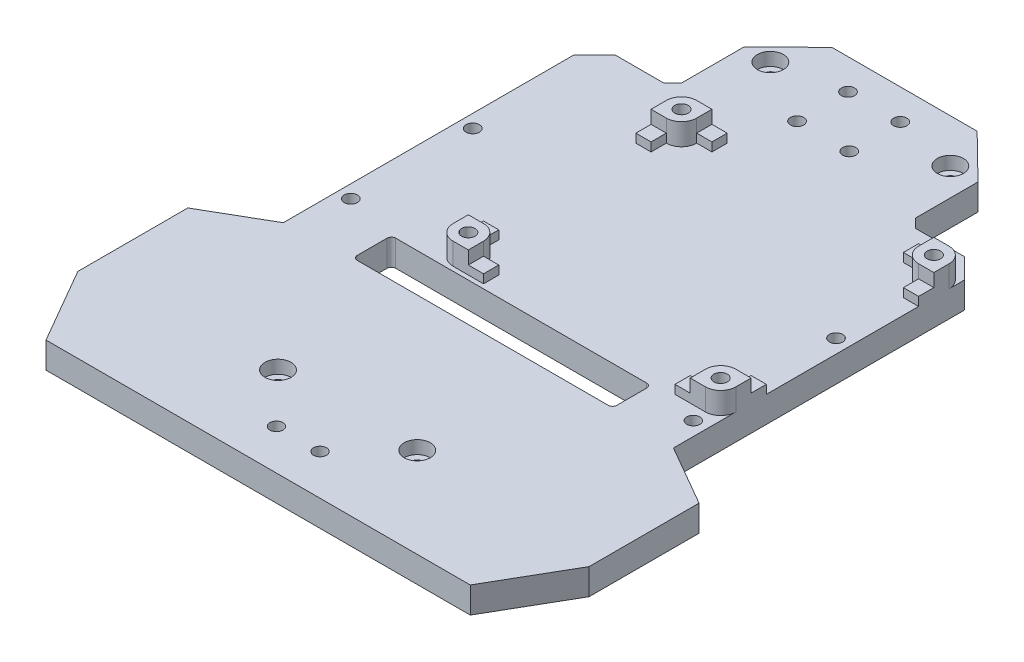
SolidWorks part; units mm, degrees
ref_plane "Front Plane" through (0, 0, 0) normal (0, 0, 1) x (1, 0, 0)
ref_plane "Top Plane" through (0, 0, 0) normal (0, 1, 0) x (1, 0, 0)
ref_plane "Right Plane" through (0, 0, 0) normal (1, 0, 0) x (0, 0, -1)
sketch "Sketch1" plane through (0, 0, 0) normal (0, 1, 0) x (1, 0, 0)
  line L0 (-16.6006, 74.2677) -> (-26.8006, 64.2675)
  line L1 (-26.8006, 64.2675) -> (-26.8006, 54.2675)
  line L2 (-26.8006, 54.2675) -> (-26.8006, 49.871)
  line L6 (-44.7582, 18.0684) -> (-44.7582, -12.842)
  line L8 (-40.1172, -36.8925) -> (-40.1172, -74.3125)
  line L9 (-40.1172, -74.3125) -> (0.0828, -74.3125)
  line L10 (0.0828, -74.3125) -> (0.0828, 74.2677) construction
  line L11 (-16.6006, 74.2677) -> (0.0828, 74.2677)
  line L12 (16.7662, 74.2677) -> (0.0828, 74.2677)
  line L13 (40.2828, -74.3125) -> (0.0828, -74.3125)
  line L14 (40.2828, -36.8925) -> (40.2828, -74.3125)
  line L16 (44.9239, 18.0684) -> (44.9239, -12.842)
  line L20 (26.9662, 54.2675) -> (26.9662, 49.871)
  line L21 (26.9662, 64.2675) -> (26.9662, 54.2675)
  line L22 (16.7662, 74.2677) -> (26.9662, 64.2675)
  line L35 (-12.597, 23.398) -> (13.1864, 23.398)
  line L36 (13.1864, 23.398) -> (13.1864, -18.272)
  line L37 (-12.597, -18.272) -> (13.1864, -18.272)
  line L38 (-12.597, 23.398) -> (-12.597, -18.272)
  line L39 (24.4264, 23.398) -> (28.1864, 23.398)
  line L40 (28.1864, 23.398) -> (28.1864, -18.272)
  line L41 (24.4264, -18.272) -> (28.1864, -18.272)
  line L42 (24.4264, 23.398) -> (24.4264, -18.272)
  line L43 (-23.837, 23.398) -> (-27.597, 23.398)
  line L44 (-27.597, 23.398) -> (-27.597, -18.272)
  line L45 (-23.837, -18.272) -> (-27.597, -18.272)
  line L46 (-23.837, 23.398) -> (-23.837, -18.272)
  line L47 (-44.7582, 18.0684) -> (-44.7582, 43.158)
  line L48 (-44.7582, 43.158) -> (-40.0718, 47.8443)
  line L49 (-40.0718, 47.8443) -> (-28.8272, 47.8443)
  line L50 (-28.8272, 47.8443) -> (-26.8006, 49.871)
  line L51 (44.9239, 18.0684) -> (44.9239, 43.158)
  line L52 (44.9239, 43.158) -> (40.2375, 47.8443)
  line L53 (40.2375, 47.8443) -> (28.9928, 47.8443)
  line L54 (28.9928, 47.8443) -> (26.9662, 49.871)
  line L55 (-40.1172, -36.8925) -> (-44.7582, -32.2514)
  line L56 (-44.7582, -32.2514) -> (-44.7582, -12.842)
  line L57 (40.2828, -36.8925) -> (44.9239, -32.2514)
  line L58 (44.9239, -32.2514) -> (44.9239, -12.842)
  dimension "D1" = 135
  dimension "D2" = 56
  dimension "D3" = 45
extrude "Boss-Extrude1" add sketch "Sketch1" along normal blind 6 contours L0 L1 L2 L50 L49 L48 L47 L6 L56 L55 L8 L9 L13 L14 L57 L58 L16 L51 L52 L53 L54 L20 L21 L22 L12 L11
sketch "Sketch2" plane through (0, 6, 0) normal (0, 1, 0) x (1, 0, 0)
  circle A0 centre (-20.7606, 64.2675) radius 1.525
  circle A1 centre (20.6062, 64.2675) radius 1.525
  circle A2 centre (-16.0772, -53.5825) radius 1.525
  circle A3 centre (15.9228, -53.5825) radius 1.525
  point P9 (-20.7606, 64.2675)
  dimension "D1" = 3.05
  dimension "D2" = 6.04
extrude "Cut-Extrude1" cut sketch "Sketch2" against normal blind 7
sketch "Sketch3" plane through (0, 6, 0) normal (0, 1, 0) x (1, 0, 0)
  circle A0 centre (-20.7606, 64.2675) radius 3
  circle A1 centre (20.6062, 64.2675) radius 3
  circle A2 centre (-16.0772, -53.5825) radius 3
  circle A3 centre (15.9228, -53.5825) radius 3
  dimension "D1" = 6
  dimension "D2" = 6
  dimension "D3" = 6
  dimension "D4" = 6
extrude "Cut-Extrude2" cut sketch "Sketch3" against normal blind 3
sketch "Sketch4" plane through (0, 6, 0) normal (0, 1, 0) x (1, 0, 0)
  line L0 (41.4239, 36.158) -> (41.4239, -5.842)
  line L1 (-13.0761, 39.658) -> (37.9239, 39.658)
  line L2 (-20.0761, 43.158) -> (44.9239, 43.158)
  line L3 (-20.0761, 43.158) -> (-20.0761, -12.842)
  line L4 (-20.0761, -12.842) -> (44.9239, -12.842)
  line L5 (44.9239, 43.158) -> (44.9239, -12.842)
  line L6 (-16.5761, 36.158) -> (-16.5761, -5.842)
  line L7 (-13.0761, -9.342) -> (37.9239, -9.342)
  circle A0 centre (-16.5761, 39.658) radius 1.55
  circle A1 centre (41.4239, 39.658) radius 1.55
  circle A2 centre (41.4239, -9.342) radius 1.55
  circle A3 centre (-16.5761, -9.342) radius 1.55
  arc A4 (37.9239, 39.658) -> (41.4239, 36.158) centre (41.4239, 39.658) ccw
  arc A5 (41.4239, -5.842) -> (37.9239, -9.342) centre (41.4239, -9.342) ccw
  arc A6 (-13.0761, -9.342) -> (-16.5761, -5.842) centre (-16.5761, -9.342) ccw
  arc A7 (-16.5761, 36.158) -> (-13.0761, 39.658) centre (-16.5761, 39.658) ccw
  dimension "D1" = 3.1
  dimension "D10" = 3.5
  dimension "D11" = 3.5
  dimension "D12" = 3.5
  dimension "D13" = 3.5
  dimension "D2" = 3.5
  dimension "D3" = 3.5
  dimension "D4" = 3.5
  dimension "D5" = 3.5
  dimension "D6" = 3.5
  dimension "D7" = 3.5
  dimension "D8" = 3.5
  dimension "D9" = 3.5
  dimension "D14" = 42
  dimension "D15" = 51
  dimension "D16" = 3.5
extrude "Boss-Extrude3" add sketch "Sketch4" along normal blind 2
fillet "Fillet1" radius 3.5 4 edges at (-20.0761, 7, -43.158) (44.9239, 7, -43.158) (-20.0761, 7, 12.842) (44.9239, 7, 12.842) tangent propagation no
sketch "Sketch5" plane through (-20.0761, 0, 0) normal (-1, 0, 0) x (0, 0, 1)
  line L0 (-39.658, 8) -> (9.342, 8) construction
  line L1 (-32.658, 8) -> (2.342, 8)
  line L2 (-32.658, 8) -> (-32.658, 6)
  line L3 (-32.658, 6) -> (2.342, 6)
  line L4 (2.342, 8) -> (2.342, 6)
  line L5 (-39.658, 6) -> (9.342, 6) construction
  point P8 (-15.158, 8)
  dimension "D1" = 35
extrude "Cut-Extrude3" cut sketch "Sketch5" against normal through all both and the other way through all
extrude "Cut-Extrude4" cut sketch "Sketch4<2>" against normal through all both and the other way through all contours A0 | A1 | A2 | A3
sketch "Sketch4<2>" plane through (0, 6, 0) normal (0, 1, 0) x (1, 0, 0) same geometry as "Sketch4"
sketch "Sketch6" plane through (0, 0, 12.842) normal (0, 0, 1) x (1, 0, 0)
  line L0 (-16.5761, 8) -> (41.4239, 8) construction
  line L1 (-9.5761, 8) -> (34.4239, 8)
  line L2 (-9.5761, 8) -> (-9.5761, 6)
  line L3 (-9.5761, 6) -> (34.4239, 6)
  line L4 (34.4239, 8) -> (34.4239, 6)
  line L5 (-16.5761, 6) -> (41.4239, 6) construction
  dimension "D1" = 3.5
  dimension "D2" = 3.5
extrude "Cut-Extrude5" cut sketch "Sketch6" against normal through all both and the other way through all
sketch "Sketch8" plane through (0, 8, 0) normal (0, 1, 0) x (1, 0, 0)
  line L0 (-13.0761, -9.342) -> (-13.0761, -12.842)
  line L1 (-16.5761, -5.842) -> (-20.0761, -5.842)
  line L2 (12.4239, -12.842) -> (12.4239, 51.535) construction
  line L3 (-9.5761, -9.342) -> (-9.5761, -12.842) construction
  line L5 (-20.0761, 15.158) -> (43.7995, 15.158) construction
  line L6 (-9.5761, -12.842) -> (-9.5761, -9.342)
  line L7 (-9.5761, -9.342) -> (-13.0761, -9.342)
  line L8 (-16.5761, -5.842) -> (-16.5761, -2.342)
  line L9 (-16.5761, -2.342) -> (-20.0761, -2.342)
  line L10 (-20.0761, -2.342) -> (-20.0761, -9.342)
  line L11 (-16.5761, -12.842) -> (-9.5761, -12.842)
  line L16 (-20.0761, -5.842) -> (-20.0761, -9.342)
  line L17 (-16.5761, -12.842) -> (-13.0761, -12.842)
  line L18 (44.9239, -2.342) -> (41.4239, -2.342) construction
  line L20 (41.4239, -12.842) -> (37.9239, -12.842)
  line L21 (44.9239, -5.842) -> (44.9239, -9.342)
  line L22 (41.4239, -5.842) -> (44.9239, -5.842)
  line L23 (37.9239, -9.342) -> (37.9239, -12.842)
  line L24 (-16.5761, 43.158) -> (-13.0761, 43.158)
  line L25 (-20.0761, 36.158) -> (-20.0761, 39.658)
  line L26 (-16.5761, 36.158) -> (-20.0761, 36.158)
  line L27 (-13.0761, 39.658) -> (-13.0761, 43.158)
  line L28 (37.9239, 39.658) -> (37.9239, 43.158)
  line L29 (41.4239, 36.158) -> (44.9239, 36.158)
  line L30 (44.9239, 36.158) -> (44.9239, 39.658)
  line L31 (41.4239, 43.158) -> (37.9239, 43.158)
  arc A0 (44.9239, -9.342) -> (41.4239, -12.842) centre (41.4239, -9.342) cw
  arc A1 (37.9239, -9.342) -> (41.4239, -5.842) centre (41.4239, -9.342) cw
  arc A2 (-13.0761, -9.342) -> (-16.5761, -5.842) centre (-16.5761, -9.342) ccw
  arc A3 (-20.0761, -9.342) -> (-16.5761, -12.842) centre (-16.5761, -9.342) ccw
  arc A4 (-13.0761, -9.342) -> (-16.5761, -5.842) centre (-16.5761, -9.342) ccw
  arc A5 (-20.0761, -9.342) -> (-16.5761, -12.842) centre (-16.5761, -9.342) ccw
  arc A6 (-20.0761, 39.658) -> (-16.5761, 43.158) centre (-16.5761, 39.658) cw
  arc A7 (-13.0761, 39.658) -> (-16.5761, 36.158) centre (-16.5761, 39.658) cw
  arc A8 (37.9239, 39.658) -> (41.4239, 36.158) centre (41.4239, 39.658) ccw
  arc A9 (44.9239, 39.658) -> (41.4239, 43.158) centre (41.4239, 39.658) ccw
  circle A10 centre (-16.5761, -9.342) radius 1.55
  circle A11 centre (41.4239, -9.342) radius 1.55
  circle A12 centre (-16.5761, 39.658) radius 1.55
  circle A13 centre (41.4239, 39.658) radius 1.55
  dimension "D2" = 22
  dimension "D3" = 17.5
  dimension "D1" = 0
extrude "Boss-Extrude4" add sketch "Sketch8" along normal blind 3
sketch "Sketch9" plane through (0, 6, 0) normal (0, 1, 0) x (1, 0, 0)
  circle A0 centre (-5.9172, 67.2677) radius 1.525
  circle A1 centre (6.0828, 67.2677) radius 1.525
  circle A2 centre (-5.9172, 55.5577) radius 1.525
  circle A3 centre (6.0828, 55.5577) radius 1.525
  dimension "D1" = 2
extrude "Cut-Extrude6" cut sketch "Sketch9" against normal blind 10
sketch "Sketch10" plane through (0, 6, 0) normal (0, 1, 0) x (1, 0, 0)
  line L0 (-44.7582, -32.2514) -> (-44.7582, 43.158) construction
  circle A0 centre (-41.7582, -11.1575) radius 1.525
  circle A1 centre (-41.7582, 16.8425) radius 1.525
  circle A2 centre (-41.7582, -11.1575) radius 1.525
  circle A3 centre (-41.7582, 16.8425) radius 1.525
  circle A4 centre (41.7582, 16.8425) radius 1.525
  circle A6 centre (-16.0772, -53.5825) radius 1.525 construction
  circle A7 centre (41.7582, -15.9575) radius 1.5
  point P10 (-41.7582, 2.8425)
  dimension "D1" = 3.05
  dimension "D7" = 3
  dimension "D2" = 3
  dimension "D3" = 56.425
  dimension "D4" = 14
  dimension "D5" = 28
  dimension "D6" = 32.8
extrude "Cut-Extrude7" cut sketch "Sketch10" against normal through all contours A0 | A1 | A4 | A7
sketch "Sketch11" plane through (0, 6, 0) normal (0, 1, 0) x (1, 0, 0)
  line L0 (40.2828, -74.3125) -> (-40.1172, -74.3125) construction
  line L1 (0, -6.05) -> (0, 6.05) construction
  circle A0 centre (-5, -65.0125) radius 1.5
  circle A1 centre (5, -65.0125) radius 1.5
  dimension "D2" = 3
  dimension "D1" = 5
  dimension "D3" = 9.3
extrude "Cut-Extrude8" cut sketch "Sketch11" against normal through all
sketch "Sketch12" plane through (0, 6, 0) normal (0, 1, 0) x (1, 0, 0)
  line L0 (-44.6754, -21.7244) -> (-58.6754, -21.7244)
  line L1 (-58.6754, -21.7244) -> (-58.6754, -74.3125)
  line L2 (-58.6754, -74.3125) -> (-40.0344, -74.3125)
  line L3 (0.0828, -62.0125) -> (0.0828, -16.7174) construction
  line L4 (58.841, -74.3125) -> (40.2, -74.3125)
  line L5 (58.841, -21.7244) -> (58.841, -74.3125)
  line L6 (44.841, -21.7244) -> (58.841, -21.7244)
  line L7 (-44.6754, -21.7244) -> (44.841, -21.7244)
  line L8 (-40.0344, -74.3125) -> (40.2, -74.3125)
  line L9 (40.2828, -74.3125) -> (-40.1172, -74.3125) construction
  line L40 (34.4239, -12.842) -> (34.4239, -9.342)
  line L41 (34.4239, -9.342) -> (37.9239, -9.342)
  line L42 (41.4239, -5.842) -> (41.4239, -2.342)
  line L43 (41.4239, -2.342) -> (44.9239, -2.342)
  line L44 (44.9239, -2.342) -> (44.9239, 32.658)
  line L45 (44.9239, 32.658) -> (41.4239, 32.658)
  line L46 (41.4239, 32.658) -> (41.4239, 36.158)
  line L47 (37.9239, 39.658) -> (34.4239, 39.658)
  line L48 (34.4239, 39.658) -> (34.4239, 43.158)
  line L49 (34.4239, 43.158) -> (41.4239, 43.158)
  line L50 (44.9239, 39.658) -> (44.9239, 43.158)
  line L51 (44.9239, 43.158) -> (40.2375, 47.8443)
  line L52 (40.2375, 47.8443) -> (28.9928, 47.8443)
  line L53 (28.9928, 47.8443) -> (26.9662, 49.871)
  line L54 (26.9662, 49.871) -> (26.9662, 64.2675)
  line L55 (26.9662, 64.2675) -> (16.7662, 74.2677)
  line L56 (16.7662, 74.2677) -> (-16.6006, 74.2677)
  line L57 (-16.6006, 74.2677) -> (-26.8006, 64.2675)
  line L58 (-26.8006, 64.2675) -> (-26.8006, 49.871)
  line L59 (-26.8006, 49.871) -> (-28.8272, 47.8443)
  line L60 (-28.8272, 47.8443) -> (-40.0718, 47.8443)
  line L61 (-40.0718, 47.8443) -> (-44.7582, 43.158)
  line L62 (-44.7582, 43.158) -> (-44.7582, -32.2514)
  line L63 (-44.7582, -32.2514) -> (-40.1172, -36.8925)
  line L64 (-40.1172, -36.8925) -> (-40.1172, -74.3125)
  line L65 (-40.1172, -74.3125) -> (40.2828, -74.3125)
  line L66 (40.2828, -74.3125) -> (40.2828, -36.8925)
  line L67 (40.2828, -36.8925) -> (44.9239, -32.2514)
  line L68 (44.9239, -32.2514) -> (44.9239, -9.342)
  line L69 (41.4239, -12.842) -> (34.4239, -12.842)
  line L92 (-44.7582, -21.7244) -> (-44.7582, -32.2514)
  line L93 (-44.7582, -32.2514) -> (-40.1172, -36.8925)
  line L94 (-40.1172, -36.8925) -> (-40.1172, -74.3125)
  line L95 (-40.1172, -74.3125) -> (40.2828, -74.3125)
  line L96 (40.2828, -74.3125) -> (40.2828, -36.8925)
  line L97 (40.2828, -36.8925) -> (44.9239, -32.2514)
  line L98 (44.9239, -32.2514) -> (44.9239, -21.7244)
  arc A4 (41.4239, -5.842) -> (37.9239, -9.342) centre (41.4239, -9.342) ccw
  arc A5 (37.9239, 39.658) -> (41.4239, 36.158) centre (41.4239, 39.658) ccw
  arc A6 (44.9239, 39.658) -> (41.4239, 43.158) centre (41.4239, 39.658) ccw
  arc A7 (41.4239, -12.842) -> (44.9239, -9.342) centre (41.4239, -9.342) ccw
  point P10 (0.0828, -74.3125)
  dimension "D1" = 0
extrude "Boss-Extrude5" add sketch "Sketch12" against normal through all contours L98 L97 L96 L4 L5 L6 | L94 L93 L92 L0 L1 L2 region at (-49.8582, 6, 49.3069) region at (50.0238, 6, 49.3069)
chamfer "Chamfer1" distance 10 angle 60 2 edges at (58.841, 3, 74.3125) (-58.6754, 3, 74.3125) first distance on face at (0.0828, 3, 74.3125)
chamfer "Chamfer2" distance 10 angle 60 2 edges at (58.841, 3, 21.7244) (-58.6754, 3, 21.7244) first distance on face at (58.841, 3, 39.3582) first distance on face at (-58.6754, 3, 39.3582)
sketch "Sketch13" plane through (0, 6, 0) normal (0, 1, 0) x (1, 0, 0)
  line L0 (-44.7582, -23.6893) -> (44.9239, -23.6893) construction
  line L1 (-29.7582, -13.842) -> (29.9239, -13.842)
  line L2 (-29.7582, -13.842) -> (-29.7582, -22.6893)
  line L3 (-29.7582, -22.6893) -> (29.9239, -22.6893)
  line L4 (29.9239, -13.842) -> (29.9239, -22.6893)
  line L5 (-16.5761, -12.842) -> (-9.5761, -12.842) construction
  line L6 (-44.7582, -23.6893) -> (-44.7582, 43.158) construction
  line L7 (44.9239, -23.6893) -> (44.9239, -9.342) construction
  dimension "D1" = 1
  dimension "D2" = 1
  dimension "D3" = 15
  dimension "D4" = 15
extrude "Cut-Extrude9" cut sketch "Sketch13" against normal through all
fillet "Fillet2" radius 1 4 edges at (29.9239, 3, 22.6893) (29.9239, 3, 13.842) (-29.7582, 3, 22.6893) (-29.7582, 3, 13.842)
